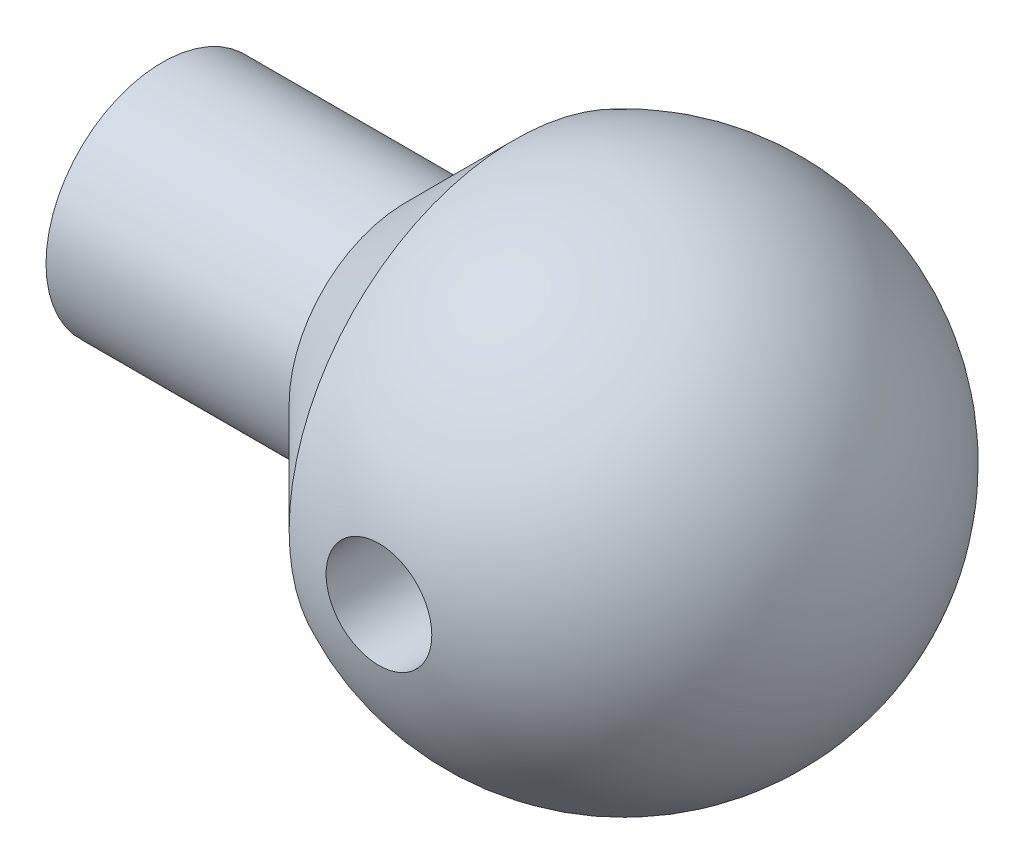
SolidWorks part; units mm, degrees
ref_plane "前视基准面" through (0, 0, 0) normal (0, 0, 1) x (1, 0, 0)
ref_plane "上视基准面" through (0, 0, 0) normal (0, 1, 0) x (1, 0, 0)
ref_plane "右视基准面" through (0, 0, 0) normal (1, 0, 0) x (0, 0, -1)
sketch "草图1" plane through (0, 0, 0) normal (0, 0, 1) x (1, 0, 0)
  line L0 (0, 0) -> (1.9828, -3.3)
  line L1 (1.9828, -3.3) -> (8.8828, -3.3)
  line L2 (0, 0) -> (20.6459, 0) construction
  line L3 (8.8828, -3.3) -> (11.9828, -6.4)
  line L5 (0, 0) -> (22.1941, 0)
  arc A0 (11.9828, -6.4) -> (22.1941, 0) centre (15.0828, 0) ccw
  point P7 (0, 0)
  point P8 (0, 0)
  point P9 (0, 0)
  point P11 (22.187, 0)
  point P12 (11.8933, -6.3104)
  point P13 (0, 0)
  point P14 (0, 0)
  dimension "D6" = 3.1
  dimension "D5" = 10
  dimension "D4" = 6.4
  dimension "D1" = 59
  dimension "D2" = 3.3
  dimension "D3" = 45
revolve "旋转1" add sketch "草图1" angle 360 about L2
sketch "草图8" plane through (0, 0, 0) normal (0, 0, 1) x (1, 0, 0)
  circle A0 centre (15.0828, 0) radius 1.5
  dimension "2" = 3
extrude "切除-拉伸1" cut sketch "草图8" against normal through all both and the other way through all
